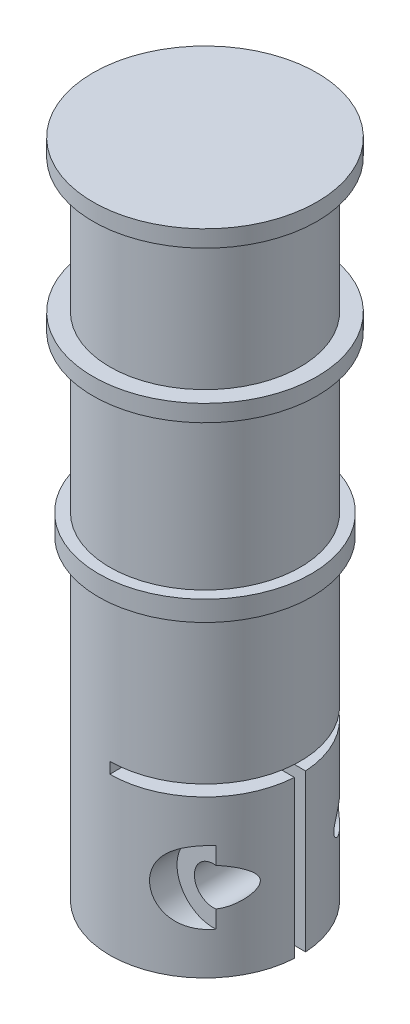
SolidWorks part; units mm, degrees
note: The reader was unsure of these and kept them because the rebuilt part matched: shared geometry of "Sketch10<3>".
material "6061 Alloy"
ref_plane "Front Plane" through (0, 0, 0) normal (0, 0, 1) x (1, 0, 0)
ref_plane "Top Plane" through (0, 0, 0) normal (0, 1, 0) x (1, 0, 0)
ref_plane "Right Plane" through (0, 0, 0) normal (1, 0, 0) x (0, 0, -1)
sketch "Sketch1" plane through (0, 0, 0) normal (0, 0, 1) x (1, 0, 0)
  line L2 (-8.5, -44) -> (-8.5, -15.8)
  line L3 (-8.5, 0) -> (-10, 0)
  line L4 (-10, 0) -> (-10, 1.5)
  line L5 (-10, 1.5) -> (-8.5, 1.5)
  line L6 (-8.5, 1.5) -> (-8.5, 13.5)
  line L7 (-8.5, 13.5) -> (-10, 13.5)
  line L8 (-10, 13.5) -> (-10, 15)
  line L9 (-10, 15) -> (0, 15)
  line L10 (0, 15) -> (0, -30)
  line L11 (-4, -44) -> (-8.5, -44)
  line L12 (-4, -30) -> (-4, -44)
  line L13 (0, -30) -> (-4, -30)
  line L14 (-8.5, -15.8) -> (-9.5, -15.8)
  line L16 (-9.5, -15.8) -> (-9.5, -14)
  line L17 (-9.5, -14) -> (-8.5, -14)
  line L18 (-8.5, -14) -> (-8.5, 0)
  dimension "D1" = 8.5
  dimension "D2" = 1.5
  dimension "D3" = 44
  dimension "D4" = 1.5
  dimension "D5" = 4
  dimension "D6" = 14
  dimension "D7" = 15
  dimension "D8" = 10
  dimension "D9" = 28.2
  dimension "D10" = 1
  dimension "D11" = 14
revolve "Revolve1" add sketch "Sketch1" angle 360 about L10
ref_plane "Plane1" through (0, 0, 8.5) normal (0, 0, 1) x (1, 0, 0)
hole_wizard "CBORE for M3 SHCS1" positions "Sketch6" profile "Sketch7" counterbore size "M3" standard "ANSI Metric"
sketch "Sketch6" plane through (0, 0, 8.5) normal (0, 0, 1) x (1, 0, 0)
  line L0 (-8.5, -44) -> (8.5, -44) construction
  line L1 (8.5, -44) -> (8.5, -15.8) construction
  point P0 (6.25, -37)
  dimension "D1" = 7
  dimension "D2" = 2.25
sketch "Sketch7" plane through (6.25, -37, 8.5) normal (1, 0, 0) x (0, -1, 0)
  line L0 (0, 0) -> (0, 9.5215)
  line L1 (0, 9.5215) -> (1.7, 8.5)
  line L2 (1.7, 8.5) -> (1.7, 3)
  line L3 (1.7, 3) -> (3.25, 3)
  line L4 (3.25, 3) -> (3.25, 0)
  line L5 (3.25, 0) -> (0, 0)
  line L10 (0, 9.5215) -> (-1.7, 8.5) construction
  line L11 (0, -6.35) -> (0, 107.95) construction
  dimension "Hole Dia." = 3.4
  dimension "Hole Depth" = 8.5
  dimension "C'Bore Dia." = 6.5
  dimension "C'Bore Depth" = 3
  dimension "Drill Angle" = 118
hole_wizard "M3x0.5 Tapped Hole1" positions "Sketch8" profile "Sketch9" tap size "M3x0.5" standard "ANSI Metric" end condition up to next
sketch "Sketch8" plane through (0, 0, 0) normal (0, 0, 1) x (1, 0, 0)
  point P1 (6.25, -37)
sketch "Sketch9" plane through (6.25, -37, 0) normal (1, 0, 0) x (0, -1, 0)
  line L0 (0, 0) -> (0, 5.7609)
  line L1 (0, 5.7609) -> (1.25, 5.7609)
  line L2 (1.25, 5.7609) -> (1.25, 0)
  line L5 (1.25, 0) -> (0, 0)
  line L11 (0, -6.35) -> (0, 107.95) construction
  dimension "Thru Tap Drill Dia." = 2.5
  dimension "Thru Tap Drill Depth" = 5.7609
cosmetic thread "Hole Thread1" parameters "D2"=3
sketch "Sketch10" plane through (0, 0, 0) normal (1, 0, 0) x (0, 0, -1)
  line L0 (-8.5, -44) -> (8.5, -44) construction
  line L1 (-0.5, -45) -> (0.5, -45)
  line L2 (-0.5, -45) -> (-0.5, -30)
  line L3 (-0.5, -30) -> (0.5, -30)
  line L4 (0.5, -45) -> (0.5, -30)
  line L5 (-8.5, -44) -> (8.5, -44) construction
  line L6 (-0.5, -30) -> (0.5, -30) construction
  line L7 (-9.5, -30) -> (-0.5, -30)
  line L8 (-9.5, -30) -> (-9.5, -29)
  line L9 (-9.5, -29) -> (9.5, -29)
  line L10 (9.5, -30) -> (9.5, -29)
  line L11 (0.5, -30) -> (9.5, -30)
  point P6 (0, -44)
  point P7 (0, -45)
  dimension "D1" = 1
  dimension "D2" = 1
  dimension "D3" = 15
  dimension "D4" = 19
  dimension "D5" = 1
extrude "Cut-Extrude1" cut sketch "Sketch10" along normal through all both and the other way through all contours L1 L4 L3 L2
extrude "Cut-Extrude2" cut sketch "Sketch10<3>" along normal blind 10 contours L3 L11 L10 L9 L8 L7
sketch "Sketch10<3>" plane through (0, 0, 0) normal (1, 0, 0) x (0, 0, -1) same geometry as "Sketch10"
